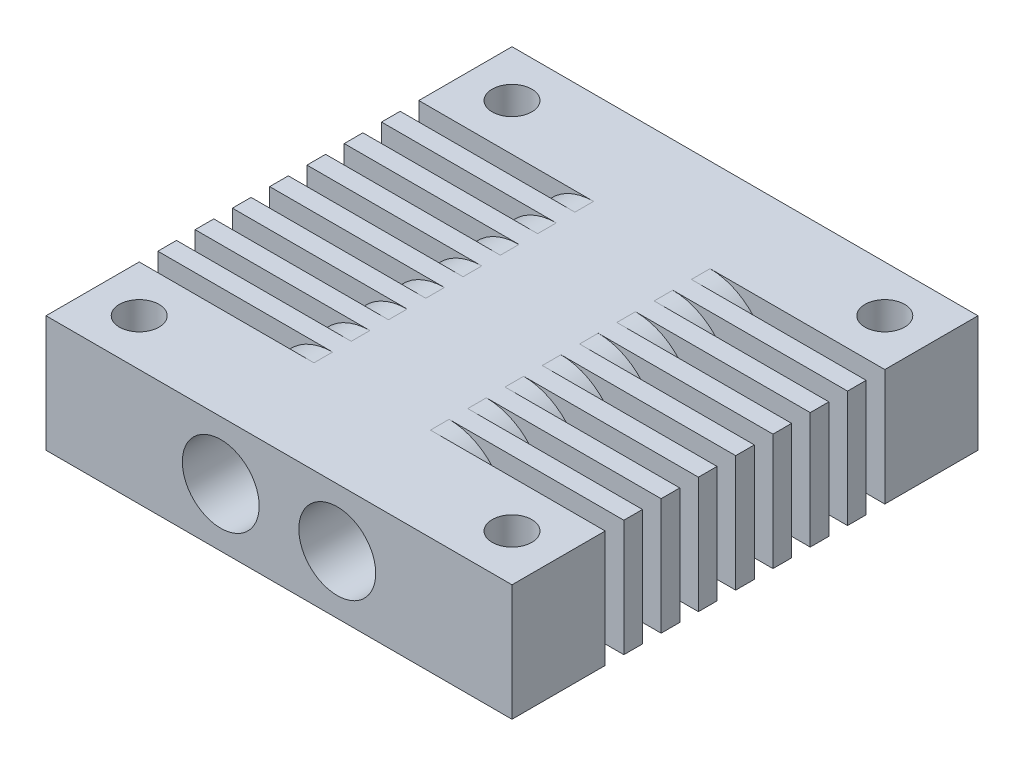
SolidWorks part; units mm, degrees
ref_plane "Plan de face" through (0, 0, 0) normal (0, 0, 1) x (1, 0, 0)
ref_plane "Plan de dessus" through (0, 0, 0) normal (0, 1, 0) x (1, 0, 0)
ref_plane "Plan de droite" through (0, 0, 0) normal (1, 0, 0) x (0, 0, -1)
sketch "Esquisse2" plane through (0, 0, 0) normal (0, 0, 1) x (1, 0, 0)
  line L1 (0, 0) -> (40, 0)
  line L2 (0, 0) -> (0, 10)
  line L3 (0, 10) -> (40, 10)
  line L4 (40, 0) -> (40, 10)
  dimension "D1" = 10
  dimension "D2" = 40
extrude "Boss.-Extru.1" add sketch "Esquisse2" along normal blind 40
sketch "Esquisse5" plane through (0, 0, 40) normal (0, 0, 1) x (1, 0, 0)
  line L0 (40, 0) -> (40, 10) construction
  line L1 (40, 10) -> (0, 10) construction
  circle A0 centre (25, 5) radius 2
  dimension "D1" = 4
  dimension "D2" = 15
  dimension "D3" = 5
hole_wizard "Diamètre du perçage Ø4.1 (4.1)1" positions "Esquisse7" profile "Esquisse6" hole size "Ø4.1" standard "ISO" end condition through all
sketch "Esquisse7" plane through (0, 0, 40) normal (0, 0, 1) x (1, 0, 0)
  point P0 (25, 5)
sketch "Esquisse6" plane through (25, 5, 40) normal (1, 0, 0) x (0, -1, 0)
  line L0 (0, 0) -> (0, 40)
  line L1 (0, 40) -> (2.05, 40)
  line L2 (2.05, 40) -> (2.05, 0)
  line L5 (2.05, 0) -> (0, 0)
  line L11 (0, -6.35) -> (0, 107.95) construction
  dimension "Diamètre du perçage jusqu'au prochain" = 4.1
  dimension "Profondeur du perçage jusqu'au prochain" = 40
hole_wizard "Dégagement M61" positions "Esquisse10" profile "Esquisse9" hole size "M6" standard "ISO"
sketch "Esquisse10" plane through (0, 0, 40) normal (0, 0, 1) x (1, 0, 0)
  point P0 (25, 5)
sketch "Esquisse9" plane through (25, 5, 40) normal (1, 0, 0) x (0, -1, 0)
  line L0 (0, 0) -> (0, 9.9828)
  line L1 (0, 9.9828) -> (3.3, 8)
  line L2 (3.3, 8) -> (3.3, 0)
  line L5 (3.3, 0) -> (0, 0)
  line L10 (0, 9.9828) -> (-3.3, 8) construction
  line L11 (0, -6.35) -> (0, 107.95) construction
  dimension "Diamètre du perçage" = 6.6
  dimension "Profondeur du perçage" = 8
  dimension "Angle de pointe" = 118
hole_wizard "Diamètre du perçage Ø6.0 (6)1" positions "Esquisse14" profile "Esquisse13" hole size "Ø6.0" standard "ISO"
sketch "Esquisse14" plane through (0, 0, 0) normal (0, 0, -1) x (-1, 0, 0)
  point P0 (-25, 5)
sketch "Esquisse13" plane through (25, 5, 0) normal (1, 0, 0) x (0, 1, 0)
  line L0 (0, 0) -> (0, 20)
  line L1 (0, 20) -> (3.05, 20)
  line L2 (3.05, 20) -> (3.05, 0)
  line L5 (3.05, 0) -> (0, 0)
  line L10 (0, 20) -> (-3.05, 20) construction
  line L11 (0, -6.35) -> (0, 107.95) construction
  dimension "Diamètre du perçage" = 6.1
  dimension "Profondeur du perçage" = 20
  dimension "Angle de pointe" = 180
sketch "Esquisse15" plane through (0, 0, 0) normal (0, -1, 0) x (1, 0, 0)
  line L0 (0, 40) -> (40, 40) construction
  line L1 (0, 40) -> (0, 0) construction
  line L2 (40, 40) -> (40, 0) construction
  line L3 (0, 0) -> (40, 0) construction
  circle A0 centre (4, 36) radius 1.5
  circle A1 centre (36, 36) radius 1.5
  circle A2 centre (36, 4) radius 1.5
  circle A3 centre (4, 4) radius 1.5
  circle A4 centre (25, 4) radius 1.5
  dimension "D1" = 3
  dimension "D2" = 3
  dimension "D3" = 3
  dimension "D4" = 3
  dimension "D5" = 3
  dimension "D14" = 4
  dimension "D6" = 4
  dimension "D7" = 4
  dimension "D8" = 4
  dimension "D9" = 4
  dimension "D10" = 4
  dimension "D11" = 4
  dimension "D12" = 4
  dimension "D13" = 4
  dimension "D15" = 25
hole_wizard "Dégagement M31" positions "Esquisse17" profile "Esquisse16" hole size "M3" standard "ISO" end condition through all
sketch "Esquisse17" plane through (0, 0, 0) normal (0, -1, 0) x (-1, 0, 0)
  point P0 (-4, -36)
  point P3 (-36, -36)
  point P6 (-36, -4)
  point P9 (-4, -4)
sketch "Esquisse16" plane through (4, 0, 36) normal (1, 0, 0) x (0, 0, -1)
  line L0 (0, 0) -> (0, 10)
  line L1 (0, 10) -> (1.7, 10)
  line L2 (1.7, 10) -> (1.7, 0)
  line L5 (1.7, 0) -> (0, 0)
  line L11 (0, -6.35) -> (0, 107.95) construction
  dimension "Diamètre du perçage jusqu'au prochain" = 3.4
  dimension "Profondeur du perçage jusqu'au prochain" = 10
hole_wizard "Dégagement M32" positions "Esquisse19" profile "Esquisse18" hole size "M3" standard "ISO"
sketch "Esquisse19" plane through (0, 0, 0) normal (0, -1, 0) x (-1, 0, 0)
  point P0 (-25, -4)
sketch "Esquisse18" plane through (25, 0, 4) normal (1, 0, 0) x (0, 0, -1)
  line L0 (0, 0) -> (0, 6.0215)
  line L1 (0, 6.0215) -> (1.7, 5)
  line L2 (1.7, 5) -> (1.7, 0)
  line L5 (1.7, 0) -> (0, 0)
  line L10 (0, 6.0215) -> (-1.7, 5) construction
  line L11 (0, -6.35) -> (0, 107.95) construction
  dimension "Diamètre du perçage" = 3.4
  dimension "Profondeur du perçage" = 5
  dimension "Angle de pointe" = 118
pattern_linear "Répétition linéaire2" count 2 spacing 10 along (-1, 0, 0) of "Dégagement M32", "Diamètre du perçage Ø6.0 (6)1", "Dégagement M61", "Diamètre du perçage Ø4.1 (4.1)1"
sketch "Esquisse20" plane through (0, 40, 40) normal (0, 0, -1) x (-1, 0, 0)
  line L0 (-15, -35) -> (-25, -35) construction
  line L1 (-15, -40) -> (-25, -40)
  line L3 (-15, -30) -> (-25, -30)
  arc A0 (-15, -40) -> (-15, -30) centre (-15, -35) ccw
  circle A1 centre (-20, -35) radius 30.0561
  arc A2 (-25, -30) -> (-25, -40) centre (-25, -35) ccw
  point P3 (-20, -35)
  dimension "D1" = 5
  dimension "D2" = 5
  dimension "D3" = 10
extrude "Enlèv. mat.-Extru.1" cut sketch "Esquisse20" along normal blind 1.6 from offset 8
pattern_linear "Répétition linéaire1" count 8 spacing 3.2 along (0, 0, -1) of "Enlèv. mat.-Extru.1"
chamfer "Chanfrein1" [suppressed] distance 0.5 angle 45
